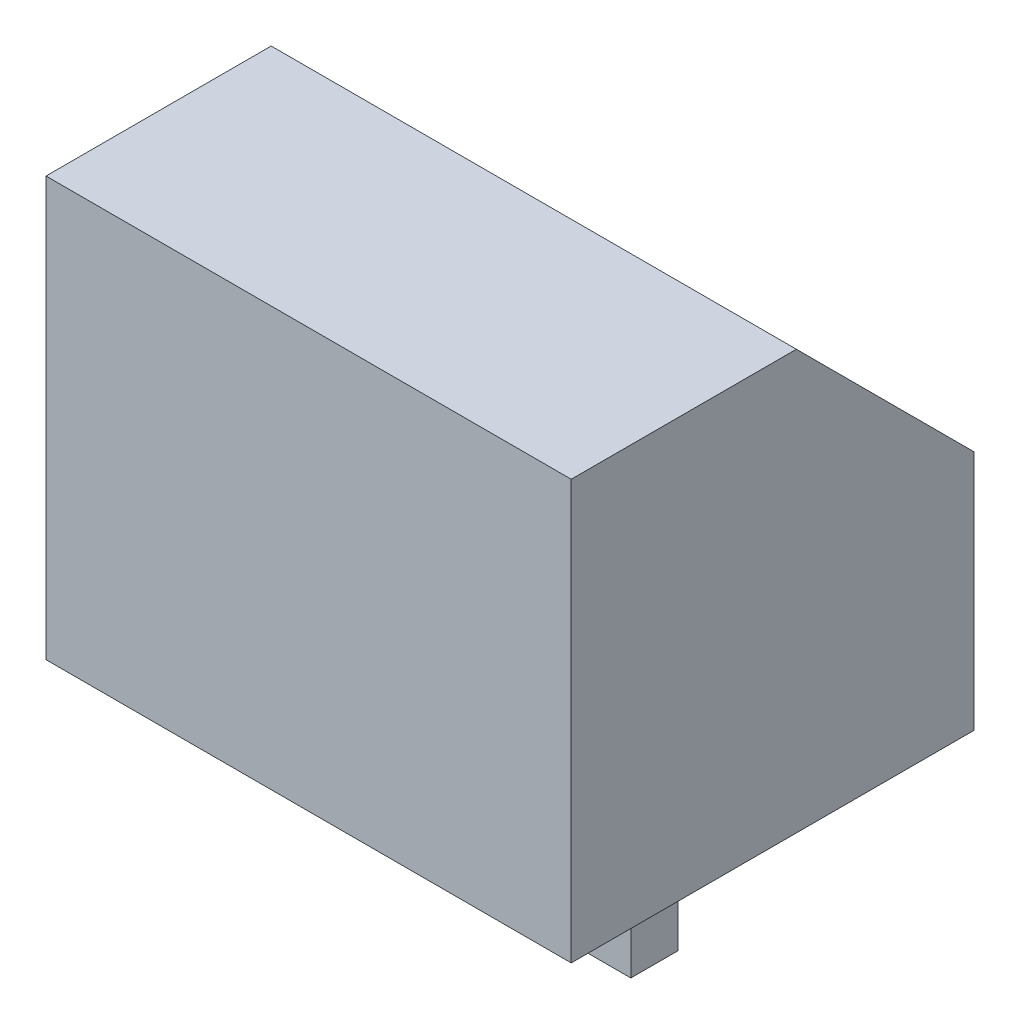
SolidWorks part; units mm, degrees
ref_plane "Front Plane" through (0, 0, 0) normal (0, 0, 1) x (1, 0, 0)
ref_plane "Top Plane" through (0, 0, 0) normal (0, 1, 0) x (1, 0, 0)
ref_plane "Right Plane" through (0, 0, 0) normal (1, 0, 0) x (0, 0, -1)
sketch "Sketch1" plane through (0, 0, 0) normal (0, 1, 0) x (1, 0, 0)
  line L1 (-10.3505, -7.9375) -> (10.3505, -7.9375)
  line L2 (-10.3505, -7.9375) -> (-10.3505, 7.9375)
  line L3 (-10.3505, 7.9375) -> (10.3505, 7.9375)
  line L4 (10.3505, -7.9375) -> (10.3505, 7.9375)
  line L5 (-10.3505, -7.9375) -> (10.3505, 7.9375) construction
  line L6 (-10.3505, 7.9375) -> (10.3505, -7.9375) construction
  point P0 (0, 0)
  dimension "D1" = 15.875
  dimension "D2" = 20.701
extrude "Boss-Extrude1" add sketch "Sketch1" along normal blind 16.51
sketch "Sketch2" plane through (0, 0, 0) normal (0, -1, 0) x (-1, 0, 0)
  line L1 (5.6896, 0.9271) -> (3.8354, 0.9271)
  line L2 (5.6896, 0.9271) -> (5.6896, -0.9271)
  line L3 (5.6896, -0.9271) -> (3.8354, -0.9271)
  line L4 (3.8354, 0.9271) -> (3.8354, -0.9271)
  line L5 (5.6896, 0.9271) -> (3.8354, -0.9271) construction
  line L6 (5.6896, -0.9271) -> (3.8354, 0.9271) construction
  line L7 (-3.8354, 0.9271) -> (-5.6896, 0.9271)
  line L8 (-3.8354, 0.9271) -> (-3.8354, -0.9271)
  line L9 (-3.8354, -0.9271) -> (-5.6896, -0.9271)
  line L10 (-5.6896, 0.9271) -> (-5.6896, -0.9271)
  line L11 (-3.8354, 0.9271) -> (-5.6896, -0.9271) construction
  line L12 (-3.8354, -0.9271) -> (-5.6896, 0.9271) construction
  line L16 (-10.3505, 7.9375) -> (-10.3505, -7.9375)
  line L17 (-10.3505, -7.9375) -> (10.3505, -7.9375)
  line L18 (10.3505, -7.9375) -> (10.3505, 7.9375)
  line L19 (10.3505, 7.9375) -> (-10.3505, 7.9375)
  line L20 (-10.3505, 7.9375) -> (-10.3505, -7.9375)
  line L21 (-10.3505, -7.9375) -> (10.3505, -7.9375)
  line L22 (10.3505, -7.9375) -> (10.3505, 7.9375)
  line L23 (10.3505, 7.9375) -> (-10.3505, 7.9375)
  point P0 (4.7625, 0)
  point P5 (-4.7625, 0)
  point P12 (0, 0)
  dimension "D1" = 9.525
  dimension "D3" = 4.7625
  dimension "D4" = 1.8542
  dimension "D2" = 0
extrude "Boss-Extrude2" add sketch "Sketch2" along normal blind 6.35 contours L1 L4 L3 L2 | L7 L10 L9 L8 region at (-4.7625, 0, 0) region at (4.7625, 0, 0)
chamfer "Chamfer1" distance 7 angle 45 1 edges at (0, 16.51, -7.9375)
ref_point "Point1"
ref_point "Point2"
ref_axis "Axis1" through (4.7625, -6.35, 0) along (0, -1, 0)
ref_axis "Axis2" through (-4.7625, -6.35, 0) along (0, -1, 0)
